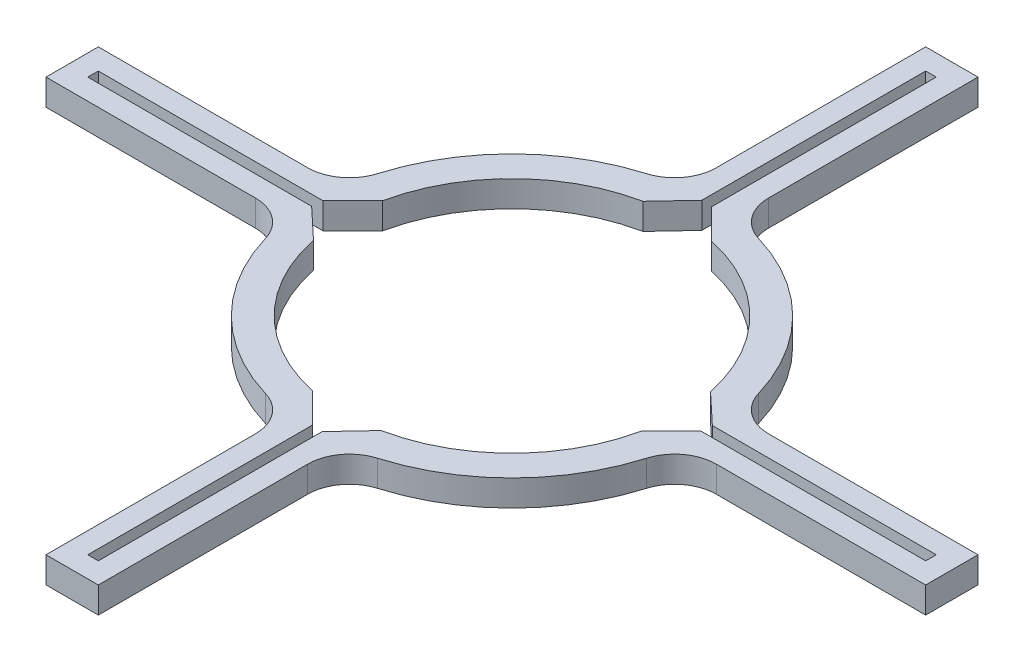
SolidWorks part; units mm, degrees
ref_plane "Front Plane" through (0, 0, 0) normal (0, 0, 1) x (1, 0, 0)
ref_plane "Top Plane" through (0, 0, 0) normal (0, 1, 0) x (1, 0, 0)
ref_plane "Right Plane" through (0, 0, 0) normal (1, 0, 0) x (0, 0, -1)
sketch "Sketch1" plane through (0, 0, 0) normal (0, 1, 0) x (1, 0, 0)
  line L0 (0, 0) -> (0, 151.5669) construction
  line L1 (-76.1251, 51.1175) -> (-1.6002, 51.1175) construction
  line L2 (-1.6002, 51.0924) -> (-1.6002, 127.3175)
  line L3 (-1.6002, 127.3175) -> (1.6002, 127.3175)
  line L4 (1.6002, 127.3175) -> (1.6002, 51.0924)
  line L5 (-7.9502, 50.4955) -> (-7.9502, 51.1175)
  line L6 (-7.9502, 133.6675) -> (7.9502, 133.6675)
  line L7 (7.9502, 133.6675) -> (7.9502, 59.7988)
  line L8 (-7.9502, 59.7988) -> (-7.9502, 133.6675)
  line L9 (7.9502, 51.1175) -> (7.9502, 50.4955)
  line L10 (1.6002, 51.1175) -> (72.3353, 51.1175) construction
  line L11 (51.0924, 1.6002) -> (127.3175, 1.6002)
  line L12 (127.3175, -1.6002) -> (51.0924, -1.6002)
  line L13 (133.6675, -7.9502) -> (59.7988, -7.9502)
  line L14 (59.7988, 7.9502) -> (133.6675, 7.9502)
  line L15 (133.6675, 7.9502) -> (133.6675, -7.9502)
  line L16 (127.3175, 1.6002) -> (127.3175, -1.6002)
  line L17 (1.6002, -51.0924) -> (1.6002, -127.3175)
  line L18 (-1.6002, -127.3175) -> (-1.6002, -51.0924)
  line L19 (-7.9502, -133.6675) -> (-7.9502, -59.7988)
  line L20 (7.9502, -59.7988) -> (7.9502, -133.6675)
  line L21 (7.9502, -133.6675) -> (-7.9502, -133.6675)
  line L22 (1.6002, -127.3175) -> (-1.6002, -127.3175)
  line L23 (-51.0924, -1.6002) -> (-127.3175, -1.6002)
  line L24 (-127.3175, 1.6002) -> (-51.0924, 1.6002)
  line L25 (-133.6675, 7.9502) -> (-59.7988, 7.9502)
  line L26 (-59.7988, -7.9502) -> (-133.6675, -7.9502)
  line L27 (-133.6675, -7.9502) -> (-133.6675, 7.9502)
  line L28 (-127.3175, -1.6002) -> (-127.3175, 1.6002)
  arc A0 (-1.6002, 51.0924) -> (-51.0924, 1.6002) centre (0, 0) ccw
  arc A1 (-7.9502, 59.7988) -> (-59.7988, 7.9502) centre (0, 0) ccw
  arc A2 (-59.7988, -7.9502) -> (-7.9502, -59.7988) centre (0, 0) ccw
  arc A3 (-51.0924, -1.6002) -> (-1.6002, -51.0924) centre (0, 0) ccw
  arc A4 (7.9502, -59.7988) -> (59.7988, -7.9502) centre (0, 0) ccw
  arc A5 (1.6002, -51.0924) -> (51.0924, -1.6002) centre (0, 0) ccw
  arc A6 (59.7988, 7.9502) -> (7.9502, 59.7988) centre (0, 0) ccw
  arc A7 (51.0924, 1.6002) -> (1.6002, 51.0924) centre (0, 0) ccw
  point P46 (0, 0)
  dimension "D1" = 102.235
  dimension "D2" = 120.65
  dimension "D3" = 76.2
  dimension "D4" = 82.55
  dimension "D5" = 1.6002
  dimension "D6" = 6.35
  dimension "D7" = 4
extrude "Boss-Extrude1" add sketch "Sketch1" along normal blind 7.9375 contours L14 A6 L7 L6 L8 A1 L25 L27 L26 A2 L19 L21 L20 A4 L13 L15 A7 L11 L16 L12 A5 L17 L22 L18 A3 L23 L28 L24 A0 L2 L3 L4 region at (0, 0, -129.8868)
fillet "Fillet2" radius 12.7 8 edges at (-7.9502, 3.9688, -59.7988) (-59.7988, 3.9688, -7.9502) (7.9502, 3.9688, -59.7988) (59.7988, 3.9688, -7.9502) (59.7988, 3.9688, 7.9502) (7.9502, 3.9688, 59.7988) (-7.9502, 3.9688, 59.7988) (-59.7988, 3.9688, 7.9502)
chamfer "Chamfer1" distance 7.9375 angle 45 8 edges at (51.0924, 3.9688, -1.6002) (51.0924, 3.9688, 1.6002) (1.6002, 3.9688, -51.0924) (-1.6002, 3.9688, -51.0924) (-51.0924, 3.9688, -1.6002) (-51.0924, 3.9688, 1.6002) (-1.6002, 3.9688, 51.0924) (1.6002, 3.9688, 51.0924) first distance on face at (31.2459, 3.9688, -31.2459) first distance on face at (89.205, 3.9688, 1.6002) first distance on face at (1.6002, 3.9688, -89.205) first distance on face at (-31.2459, 3.9688, -31.2459) first distance on face at (-89.205, 3.9688, -1.6002) first distance on face at (-31.2459, 3.9688, 31.2459) first distance on face at (-1.6002, 3.9688, 89.205) first distance on face at (31.2459, 3.9688, 31.2459)
